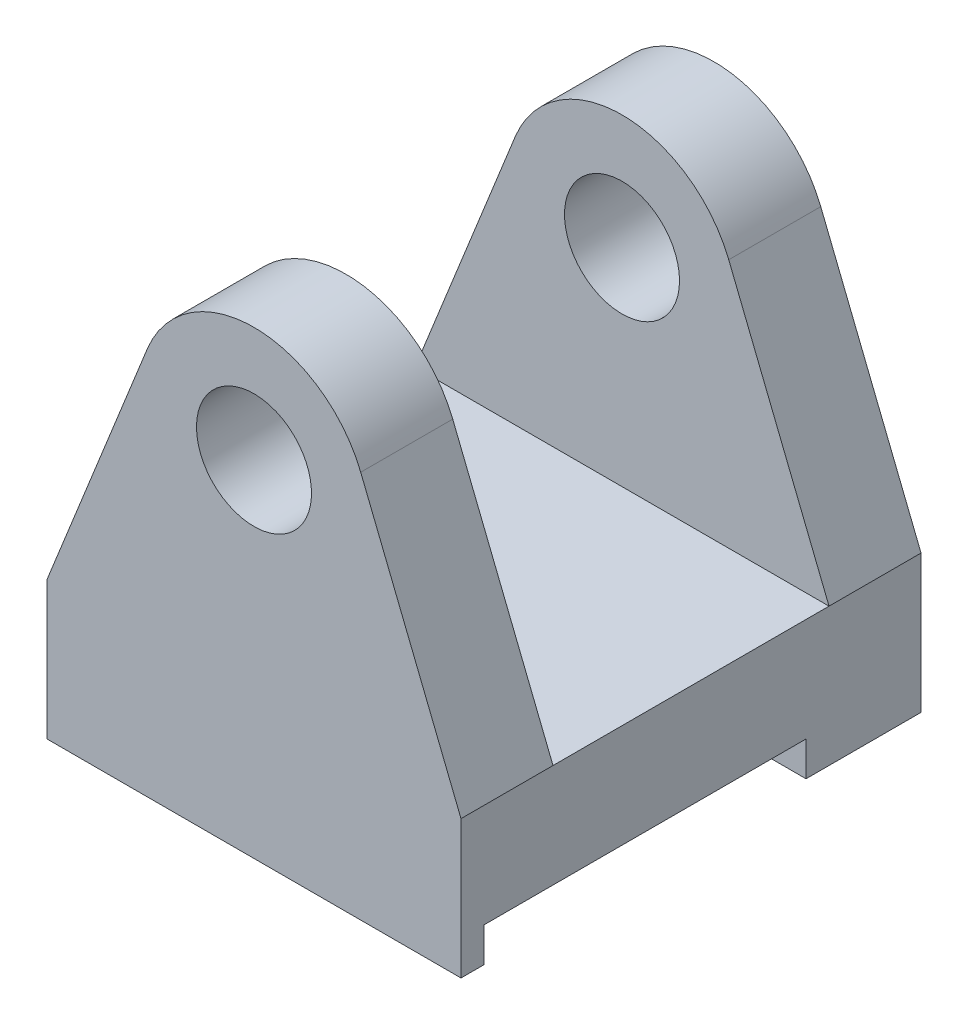
SolidWorks part; units mm, degrees
material "Plain Carbon Steel"
ref_plane "Front Plane" through (0, 0, 0) normal (0, 0, 1) x (1, 0, 0)
ref_plane "Top Plane" through (0, 0, 0) normal (0, 1, 0) x (1, 0, 0)
ref_plane "Right Plane" through (0, 0, 0) normal (1, 0, 0) x (0, 0, -1)
sketch "Sketch2" plane through (0, 0, 0) normal (0, 1, 0) x (1, 0, 0)
  line L1 (-9, -10) -> (9, -10)
  line L2 (-9, -10) -> (-9, 10)
  line L3 (-9, 10) -> (9, 10)
  line L4 (9, -10) -> (9, 10)
  line L5 (-9, -10) -> (9, 10) construction
  line L6 (-9, 10) -> (9, -10) construction
  point P0 (0, 0)
  dimension "D1" = 18
  dimension "D2" = 20
extrude "Boss-Extrude1" add sketch "Sketch2" along normal blind 6
sketch "Sketch4" plane through (0, 0, 0) normal (0, 0, 1) x (1, 0, 0)
  line L0 (0, 0) -> (0, 15) construction
  line L1 (-9, 0) -> (9, 0) construction
  line L2 (-4.6402, 16.8624) -> (-9, 6)
  line L3 (4.6402, 16.8624) -> (9, 6)
  line L4 (-9, 6) -> (9, 6)
  arc A0 (4.6402, 16.8624) -> (-4.6402, 16.8624) centre (0, 15) ccw
  circle A1 centre (0, 15) radius 2.5
  dimension "D1" = 5
  dimension "D2" = 5
  dimension "D3" = 15
extrude "Boss-Extrude2" add sketch "Sketch4" against normal blind 4 from surface starting at face at (0, 3, 10)
extrude "Boss-Extrude3" add sketch "Sketch4<2>" along normal blind 4 from surface starting at face at (0, 3, -10)
sketch "Sketch4<2>" plane through (0, 0, 0) normal (0, 0, 1) x (1, 0, 0) same geometry as "Sketch4"
sketch "Sketch5" plane through (-9, 0, 0) normal (-1, 0, 0) x (0, 0, 1)
  line L0 (-10, 0) -> (10, 0) construction
  line L1 (-5, 1.5) -> (9, 1.5)
  line L2 (-5, 1.5) -> (-5, 0)
  line L3 (-5, 0) -> (9, 0)
  line L5 (9, 1.5) -> (9, 0)
  line L6 (10, 6) -> (10, 0) construction
  dimension "D1" = 1
  dimension "D2" = 1.5
  dimension "D3" = 14
extrude "Cut-Extrude1" cut sketch "Sketch5" against normal through all
